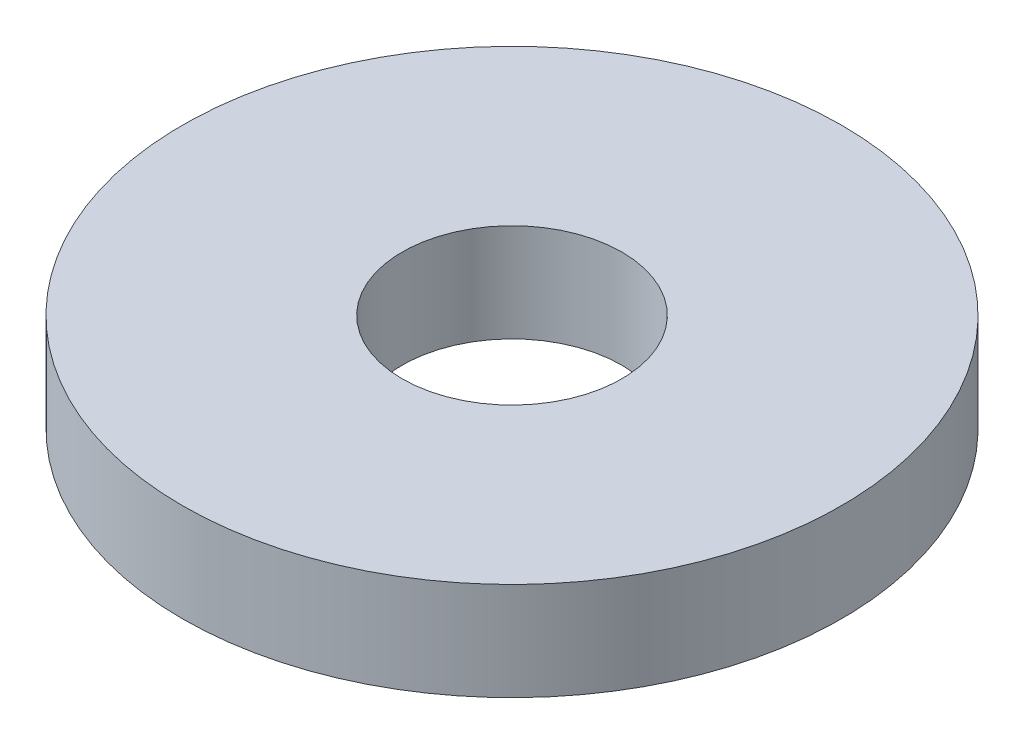
SolidWorks part; units mm, degrees
ref_plane "Front Plane" through (0, 0, 0) normal (0, 0, 1) x (1, 0, 0)
ref_plane "Top Plane" through (0, 0, 0) normal (0, 1, 0) x (1, 0, 0)
ref_plane "Right Plane" through (0, 0, 0) normal (1, 0, 0) x (0, 0, -1)
sketch "Sketch1" plane through (0, 0, 0) normal (0, 1, 0) x (1, 0, 0)
  circle A0 centre (0, 0) radius 97.5
  dimension "FLANGE_OD" = 195
extrude "Boss-Extrude1" add sketch "Sketch1" along normal blind 29
sketch "Sketch2" plane through (0, 0, 0) normal (0, 1, 0) x (1, 0, 0)
  circle A0 centre (0, 0) radius 32.5
  dimension "BORE_D" = 65
extrude "Cut-Extrude1" cut sketch "Sketch2" along normal through all
sketch "Sketch3" plane through (0, 29, 0) normal (0, 1, 0) x (1, 0, 0)
  circle A0 centre (0, 0) radius 26.9078 construction
  circle A1 centre (-26.9078, 0) radius 3.2495
  dimension "BOLT_D" = 6.499
  dimension "BOLT_PCD" = 53.8156
extrude "Cut-Extrude2" cut sketch "Sketch3" against normal blind 28.8402 rebuild error yes
pattern_circular "CirPattern1" count 6 over 360 rebuild error yes
